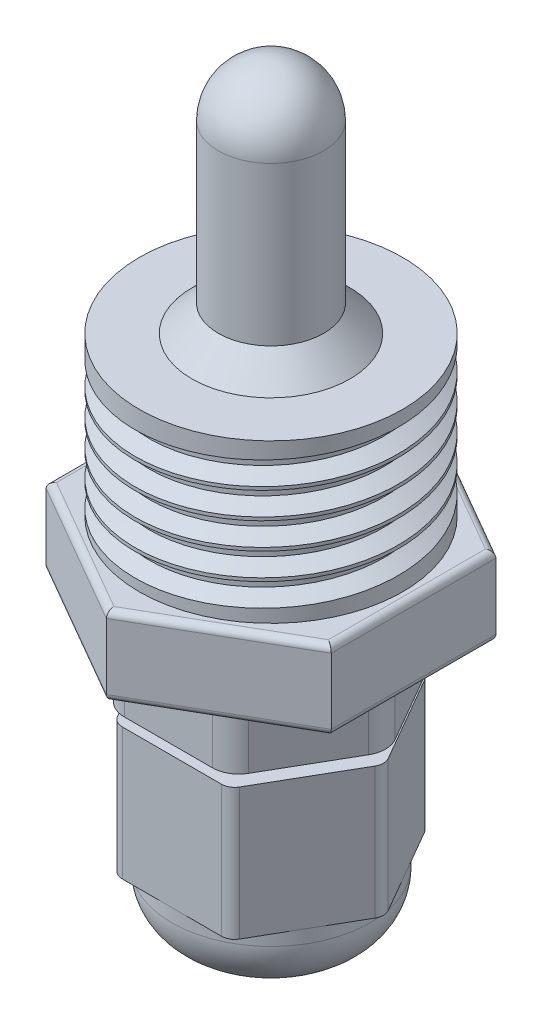
SolidWorks part; units mm, degrees
material "Сталь 20 ГОСТ 1050-88"
ref_plane "Спереди" through (0, 0, 0) normal (0, 0, 1) x (1, 0, 0)
ref_plane "Сверху" through (0, 0, 0) normal (0, 1, 0) x (1, 0, 0)
ref_plane "Справа" through (0, 0, 0) normal (1, 0, 0) x (0, 0, -1)
sketch "Эскиз1" plane through (0, 0, 0) normal (0, 1, 0) x (1, 0, 0)
  circle A0 centre (0, 0) radius 12.5
  dimension "D1" = 25
extrude "Бобышка-Вытянуть1" add sketch "Эскиз1" along normal blind 6
sketch "Эскиз2" plane through (0, 6, 0) normal (0, 1, 0) x (1, 0, 0)
  circle A0 centre (0, 0) radius 10
  dimension "D1" = 20
extrude "Бобышка-Вытянуть2" add sketch "Эскиз2" along normal blind 12
sketch "Эскиз3" plane through (0, 18, 0) normal (0, 1, 0) x (1, 0, 0)
  circle A0 centre (0, 0) radius 4
  dimension "D1" = 8
extrude "Бобышка-Вытянуть3" add sketch "Эскиз3" along normal blind 18
fillet "Скругление2" radius 4 1 edges at (0, 36, 4)
chamfer "Фаска1" distance 2 angle 45 1 edges at (0, 18, 4)
thread "G1/2" pitch 2 method cut profile "Профиль резьбы1" start angle 0, offset 0, length 10, pitch 2, diameter 20
ref_plane "Плоскость1" through (-10, 18, 0) normal (0, 0, 1) x (-1, 0, 0)
sketch "Профиль резьбы1" plane through (-10, 18, 0) normal (0, 0, 1) x (-1, 0, 0)
  line L0 (0, 0) -> (0, 2) construction
  line L11 (0, 0) -> (0, 1.75)
  line L12 (0, 1.75) -> (-1.0825, 1.125)
  line L13 (-1.0825, 1.125) -> (-1.0825, 0.625)
  line L15 (-1.0825, 0.625) -> (0, 0)
  line L17 (-1.0825, 0.875) -> (0, 0.875) construction
  point P2 (0, 0)
  dimension "Pitch" = 2
  dimension "Profile_Angle" = 60
  dimension "Profile_Land" = 0.5
  dimension "Profile_Height" = 1.0825
sketch "Эскиз6" plane through (0, 0, 0) normal (0, -1, 0) x (1, 0, 0)
  line L1 (0, 12.5) -> (-10.8253, 6.25)
  line L2 (-10.8253, 6.25) -> (-10.8253, -6.25)
  line L3 (-10.8253, -6.25) -> (0, -12.5)
  line L4 (0, -12.5) -> (10.8253, -6.25)
  line L5 (10.8253, -6.25) -> (10.8253, 6.25)
  line L6 (10.8253, 6.25) -> (0, 12.5)
  circle A0 centre (0, 0) radius 12.5
  circle A1 centre (0, 0) radius 10.8253 construction
  circle M7 centre (0, 0) radius 12.5
extrude "Вырез-Вытянуть1" cut sketch "Эскиз6" against normal blind 18 contours L1 M7 | L2 M7 | L3 M7 | L4 M7 | L5 M7 | L6 M7 region at (5.7496, 0, 9.9586) region at (-5.7496, 0, 9.9586) region at (-11.4992, 0, 0) region at (11.4992, 0, 0) region at (-5.7496, 0, -9.9586) region at (5.7496, 0, -9.9586)
fillet "Скругление3" radius 0.5 12 edges at (10.8253, 0, 0) (5.4127, 0, -9.375) (-5.4127, 0, -9.375) (-10.8253, 0, 0) (-5.4127, 0, 9.375) (5.4127, 0, 9.375) (-10.8253, 6, 0) (-5.4127, 6, 9.375) (-5.4127, 6, -9.375) (5.4127, 6, -9.375) (10.8253, 6, 0) (5.4127, 6, 9.375)
sketch "Эскиз7" plane through (0, 0, 0) normal (0, -1, 0) x (1, 0, 0)
  line L1 (9, 0) -> (4.5, 7.7942)
  line L2 (4.5, 7.7942) -> (-4.5, 7.7942)
  line L3 (-4.5, 7.7942) -> (-9, 0)
  line L4 (-9, 0) -> (-4.5, -7.7942)
  line L5 (-4.5, -7.7942) -> (4.5, -7.7942)
  line L6 (4.5, -7.7942) -> (9, 0)
  circle A1 centre (0, 0) radius 7.7942 construction
extrude "Бобышка-Вытянуть4" add sketch "Эскиз7" along normal blind 5
fillet "Скругление4" radius 2 6 edges at (4.5, -2.5, -7.7942) (9, -2.5, 0) (4.5, -2.5, 7.7942) (-4.5, -2.5, 7.7942) (-9, -2.5, 0) (-4.5, -2.5, -7.7942)
sketch "Эскиз8" plane through (0, -5, 0) normal (0, -1, 0) x (1, 0, 0)
  circle A0 centre (0, 0) radius 4
  dimension "D1" = 8
extrude "Бобышка-Вытянуть5" add sketch "Эскиз8" along normal blind 1
sketch "Эскиз9" plane through (0, -6, 0) normal (0, -1, 0) x (1, 0, 0)
  line L1 (-8.6906, 0) -> (-4.3453, -7.5263)
  line L2 (-4.3453, -7.5263) -> (4.3453, -7.5263)
  line L3 (4.3453, -7.5263) -> (8.6906, 0)
  line L4 (8.6906, 0) -> (4.3453, 7.5263)
  line L5 (4.3453, 7.5263) -> (-4.3453, 7.5263)
  line L6 (-4.3453, 7.5263) -> (-8.6906, 0)
  circle A1 centre (0, 0) radius 7.5263 construction
extrude "Бобышка-Вытянуть6" add sketch "Эскиз9" along normal blind 10
sketch "Эскиз10" plane through (0, -16, 0) normal (0, -1, 0) x (1, 0, 0)
  circle A0 centre (0, 0) radius 7.5263
extrude "Бобышка-Вытянуть7" add sketch "Эскиз10" along normal blind 5
fillet "Скругление5" radius 1 6 edges at (4.3453, -11, 7.5263) (8.6906, -11, 0) (4.3453, -11, -7.5263) (-4.3453, -11, -7.5263) (-8.6906, -11, 0) (-4.3453, -11, 7.5263)
fillet "Скругление6" radius 4 1 edges at (0, -21, -7.5263)
